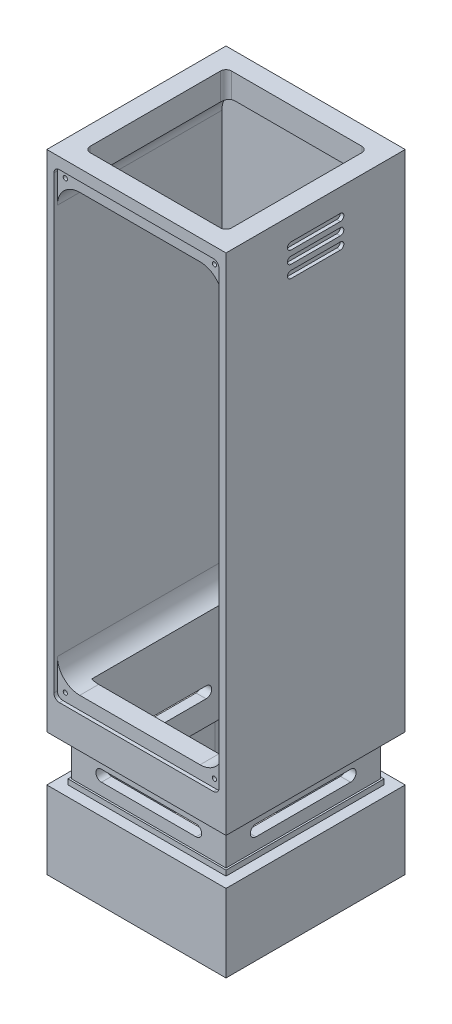
SolidWorks part; units mm, degrees
ref_plane "Front Plane" through (0, 0, 0) normal (0, 0, 1) x (1, 0, 0)
ref_plane "Top Plane" through (0, 0, 0) normal (0, 1, 0) x (1, 0, 0)
ref_plane "Right Plane" through (0, 0, 0) normal (1, 0, 0) x (0, 0, -1)
sketch "Sketch1" plane through (0, 0, 0) normal (0, 1, 0) x (1, 0, 0)
  line L0 (6.35, 44.45) -> (44.45, 44.45)
  line L1 (0, 0) -> (50.8, 0)
  line L2 (0, 0) -> (0, 50.8)
  line L3 (0, 50.8) -> (50.8, 50.8)
  line L4 (50.8, 0) -> (50.8, 50.8)
  line L5 (44.45, 6.35) -> (44.45, 44.45)
  line L6 (6.35, 6.35) -> (44.45, 6.35)
  line L7 (6.35, 6.35) -> (6.35, 44.45)
  dimension "D1" = 50.8
  dimension "D2" = 6.35
extrude "Boss-Extrude1" add sketch "Sketch1" along normal blind 178
sketch "Sketch2" plane through (0, 0, 0) normal (0, -1, 0) x (1, 0, 0)
  line L0 (47.8, -3) -> (3, -3)
  line L1 (3, -3) -> (3, -47.8)
  line L2 (3, -47.8) -> (47.8, -47.8)
  line L3 (47.8, -47.8) -> (47.8, -3)
  line L4 (6.35, -44.45) -> (44.45, -44.45)
  line L5 (6.35, -6.35) -> (6.35, -44.45)
  line L6 (44.45, -6.35) -> (6.35, -6.35)
  line L7 (44.45, -44.45) -> (44.45, -6.35)
  line L8 (6.35, -44.45) -> (44.45, -44.45)
  line L9 (6.35, -6.35) -> (6.35, -44.45)
  line L10 (44.45, -6.35) -> (6.35, -6.35)
  line L11 (44.45, -44.45) -> (44.45, -6.35)
  line L12 (0, -50.8) -> (0, 0) construction
  dimension "D2" = 3
  dimension "D1" = 0
extrude "Cut-Extrude1" cut sketch "Sketch2" against normal blind 20
sketch "Sketch3" plane through (0, 0, 0) normal (0, 0, 1) x (1, 0, 0)
  line L0 (0, 0) -> (50.8, 0) construction
  line L1 (2, 171.15) -> (48.8, 171.15)
  line L2 (2, 171.15) -> (2, 47.675)
  line L3 (2, 47.675) -> (48.8, 47.675)
  line L4 (48.8, 171.15) -> (48.8, 47.675)
  line L5 (0, 178) -> (0, 0) construction
  line L6 (50.8, 178) -> (50.8, 0) construction
  line L7 (0, 178) -> (50.8, 178) construction
  dimension "D1" = 47.675
  dimension "D2" = 2
  dimension "D3" = 2
  dimension "D4" = 6.85
extrude "Cut-Extrude2" cut sketch "Sketch3" against normal blind 47.625
sketch "Sketch4" plane through (0, 0, 0) normal (0, 0, 1) x (1, 0, 0)
  line L0 (0, 178) -> (0, 0) construction
  line L2 (0, 40) -> (0, 24)
  line L3 (0, 24) -> (50.8, 24)
  line L4 (50.8, 40) -> (50.8, 24)
  line L5 (50.8, 178) -> (50.8, 0) construction
  line L6 (0, 0) -> (50.8, 0) construction
  line L10 (0, 40) -> (50.8, 40)
  dimension "D1" = 24
  dimension "D2" = 16
extrude "Cut-Extrude3" [suppressed] cut sketch "Sketch4" against normal blind 3.175
sketch "Sketch5" [suppressed] plane through (0, 0, 0) normal (0, 0, 1) x (1, 0, 0)
  line L0 (50.8, 40) -> (0, 40) construction
  line L3 (0, 40) -> (3, 40)
  line L5 (0, 24) -> (50.8, 24) construction
  line L8 (0, 24) -> (3, 24)
  line L10 (0, 40) -> (0, 24)
  line L11 (3, 40) -> (3, 24)
  line L12 (0, 24) -> (0, 0) construction
  dimension "D1" = 3
extrude "Cut-Extrude4" [suppressed] cut sketch "Sketch5" against normal through all
ref_plane "Plane1" through (0, 0, -25.4) normal (0, 0, 1) x (1, 0, 0)
ref_plane "Plane2" through (25.4, 0, 0) normal (-1, 0, 0) x (0, 0, 1)
sketch "Sketch6" plane through (0, 0, 0) normal (-1, 0, 0) x (0, 0, 1)
  line L0 (-32.4, 170.5) -> (-18.4, 170.5) construction
  line L1 (-32.4, 171.5) -> (-18.4, 171.5)
  line L2 (-32.4, 169.5) -> (-18.4, 169.5)
  line L3 (-32.4, 167) -> (-18.4, 167) construction
  line L4 (-32.4, 168) -> (-18.4, 168)
  line L5 (-32.4, 166) -> (-18.4, 166)
  line L6 (-32.4, 163.5) -> (-18.4, 163.5) construction
  line L9 (-32.4, 164.5) -> (-18.4, 164.5)
  line L10 (-32.4, 162.5) -> (-18.4, 162.5)
  line L11 (-25.4, 170.5) -> (-25.4, 167) construction
  line L12 (-25.4, 167) -> (-25.4, 163.5) construction
  line L13 (-25.4, 170.5) -> (-25.4, 178) construction
  line L14 (-50.8, 178) -> (0, 178) construction
  arc A0 (-32.4, 171.5) -> (-32.4, 169.5) centre (-32.4, 170.5) ccw
  arc A1 (-18.4, 169.5) -> (-18.4, 171.5) centre (-18.4, 170.5) ccw
  arc A2 (-32.4, 168) -> (-32.4, 166) centre (-32.4, 167) ccw
  arc A3 (-18.4, 166) -> (-18.4, 168) centre (-18.4, 167) ccw
  arc A6 (-32.4, 164.5) -> (-32.4, 162.5) centre (-32.4, 163.5) ccw
  arc A7 (-18.4, 162.5) -> (-18.4, 164.5) centre (-18.4, 163.5) ccw
  point P2 (-25.4, 170.5)
  point P9 (-25.4, 167)
  point P16 (-25.4, 163.5)
  point P25 (-33.4, 163.5)
  point P26 (-17.4, 163.5)
  dimension "D1" = 3.5
  dimension "D2" = 2
  dimension "D3" = 7.5
  dimension "D4" = 16
extrude "Cut-Extrude5" cut sketch "Sketch6" against normal blind 1
mirror "Mirror1" [suppressed] about plane through (0, 0, -25.4) normal (0, 0, 1)
mirror "Mirror2" about plane through (25.4, 0, 0) normal (-1, 0, 0) of "Cut-Extrude5", "Cut-Extrude4"
sketch "Sketch7" plane through (0, 0, 0) normal (0, 0, 1) x (1, 0, 0)
  line L0 (0, 178) -> (50.8, 178) construction
  line L1 (2, 171.15) -> (48.8, 171.15)
  line L2 (2, 171.15) -> (2, 174.825)
  line L3 (2, 174.825) -> (48.8, 174.825)
  line L4 (48.8, 171.15) -> (48.8, 174.825)
  line L6 (2, 47.675) -> (48.8, 47.675)
  line L7 (2, 47.675) -> (2, 44)
  line L8 (2, 44) -> (48.8, 44)
  line L9 (48.8, 47.675) -> (48.8, 44)
  dimension "D1" = 3.175
extrude "Cut-Extrude6" cut sketch "Sketch7" against normal blind 1
fillet "Fillet1" radius 1.5875 4 edges at (48.8, 174.825, -0.5) (2, 174.825, -0.5) (48.8, 44, -0.5) (2, 44, -0.5)
sketch "Sketch8" plane through (0, 178, 0) normal (0, 1, 0) x (1, 0, 0)
  line L1 (6.9375, 45.45) -> (43.8625, 45.45)
  line L2 (5.35, 43.8625) -> (5.35, 6.9375)
  line L3 (6.9375, 5.35) -> (43.8625, 5.35)
  line L4 (45.45, 43.8625) -> (45.45, 6.9375)
  line L8 (6.35, 44.45) -> (6.35, 6.35) construction
  line L10 (6.35, 6.35) -> (44.45, 6.35) construction
  line L11 (44.45, 6.35) -> (44.45, 44.45) construction
  arc A0 (43.8625, 45.45) -> (45.45, 43.8625) centre (43.8625, 43.8625) cw
  arc A1 (45.45, 6.9375) -> (43.8625, 5.35) centre (43.8625, 6.9375) cw
  arc A2 (6.9375, 5.35) -> (5.35, 6.9375) centre (6.9375, 6.9375) cw
  arc A3 (5.35, 43.8625) -> (6.9375, 45.45) centre (6.9375, 43.8625) cw
  dimension "D1" = 1.5875
  dimension "D2" = 1
  dimension "D3" = 1
  dimension "D4" = 1
extrude "Cut-Extrude7" cut sketch "Sketch8" against normal up to next
hole_wizard "#0-80 Tapped Hole1" positions "Sketch12" profile "Sketch14" tap size "#0-80" standard "ANSI Inch"
sketch "Sketch12" plane through (0, 0, -1) normal (0, 0, 1) x (1, 0, 0)
  line L2 (4.2542, 172.571) -> (4.2542, 46.286) construction
  line L3 (4.2542, 46.286) -> (46.5138, 46.286) construction
  line L4 (46.5138, 46.286) -> (46.5138, 172.571) construction
  line L5 (46.5138, 172.571) -> (4.2542, 172.571) construction
  line L8 (0, 178) -> (0, 0) construction
  line L9 (0, 178) -> (50.8, 178) construction
  line L10 (50.8, 178) -> (50.8, 0) construction
  point P0 (4.2542, 172.571)
  point P3 (46.5138, 172.571)
  point P6 (4.2542, 46.286)
  point P9 (46.5138, 46.286)
  dimension "D1" = 4.2542
  dimension "D2" = 5.429
  dimension "D3" = 4.2862
  dimension "D4" = 126.285
sketch "Sketch14" plane through (4.2542, 172.571, -1) normal (1, 0, 0) x (0, -1, 0)
  line L0 (0, 0) -> (0, 3.3576)
  line L1 (0, 3.3576) -> (0.5956, 2.9997)
  line L2 (0.5956, 2.9997) -> (0.5956, 0)
  line L5 (0.5956, 0) -> (0, 0)
  line L10 (0, 3.3576) -> (-0.5956, 2.9997) construction
  line L11 (0, -6.35) -> (0, 107.95) construction
  dimension "Tap Drill Dia." = 1.1913
  dimension "Tap Drill Depth" = 2.9997
  dimension "Drill Angle" = 118
cosmetic thread "Hole Thread5" parameters "D1"=3.048, "D2"=1.524
cosmetic thread "Hole Thread6" parameters "D1"=3.048, "D2"=1.524
cosmetic thread "Hole Thread7" parameters "D1"=3.048, "D2"=1.524
cosmetic thread "Hole Thread8" parameters "D1"=3.048, "D2"=1.524
sketch "Sketch15" [suppressed] plane through (0, 0, -3.175) normal (0, 0, 1) x (1, 0, 0)
  line L0 (11.9875, 32) -> (38.8125, 32) construction
  line L1 (11.9875, 33.5875) -> (38.8125, 33.5875)
  line L2 (11.9875, 30.4125) -> (38.8125, 30.4125)
  line L3 (11.9875, 32) -> (3, 32) construction
  line L4 (3, 24) -> (3, 40) construction
  line L5 (38.8125, 32) -> (47.8, 32) construction
  line L6 (47.8, 24) -> (47.8, 40) construction
  arc A0 (11.9875, 33.5875) -> (11.9875, 30.4125) centre (11.9875, 32) ccw
  arc A1 (38.8125, 30.4125) -> (38.8125, 33.5875) centre (38.8125, 32) ccw
  point P2 (25.4, 32)
  point P17 (10.4, 32)
  point P18 (40.4, 32)
  dimension "D1" = 3.175
  dimension "D2" = 30
extrude "Cut-Extrude8" [suppressed] cut sketch "Sketch15" against normal through all
sketch "Sketch16" [suppressed] plane through (3, 0, 0) normal (-1, 0, 0) x (0, 0, 1)
  line L0 (-38.8125, 32) -> (-11.9875, 32) construction
  line L1 (-38.8125, 33.5875) -> (-11.9875, 33.5875)
  line L2 (-38.8125, 30.4125) -> (-11.9875, 30.4125)
  line L3 (-38.8125, 32) -> (-47.625, 32) construction
  line L4 (-47.625, 24) -> (-47.625, 40) construction
  line L5 (-11.9875, 32) -> (-3.175, 32) construction
  line L6 (-3.175, 24) -> (-3.175, 40) construction
  arc A0 (-38.8125, 33.5875) -> (-38.8125, 30.4125) centre (-38.8125, 32) ccw
  arc A1 (-11.9875, 30.4125) -> (-11.9875, 33.5875) centre (-11.9875, 32) ccw
  point P2 (-25.4, 32)
  point P15 (-40.4, 32)
  point P16 (-10.4, 32)
  dimension "D1" = 3.175
  dimension "D2" = 30
extrude "Cut-Extrude9" [suppressed] cut sketch "Sketch16" against normal through all
sketch "Sketch17" [suppressed] plane through (0, 0, -3.175) normal (0, 0, 1) x (1, 0, 0)
  line L0 (3, 24) -> (3, 40) construction
  line L1 (3, 37.0668) -> (47.8, 37.0668)
  line L2 (3, 37.0668) -> (3, 27.0668)
  line L3 (3, 27.0668) -> (47.8, 27.0668)
  line L4 (47.8, 37.0668) -> (47.8, 27.0668)
  line L5 (47.8, 24) -> (47.8, 40) construction
  dimension "D1" = 10
extrude "Cut-Extrude10" [suppressed] cut sketch "Sketch17" against normal blind 0.5
sketch "Sketch18" [suppressed] plane through (0, 0, -3.175) normal (0, 0, 1) x (1, 0, 0)
  line L0 (8.6937, 29) -> (42.1062, 29) construction
  line L1 (8.6937, 29.7938) -> (42.1062, 29.7938)
  line L2 (8.6937, 28.2062) -> (42.1062, 28.2062)
  line L3 (25.4, 29) -> (25.4, 24) construction
  line L4 (0, 24) -> (50.8, 24) construction
  line L5 (8.6937, 35) -> (42.1062, 35) construction
  line L6 (8.6937, 35.7938) -> (42.1062, 35.7938)
  line L7 (8.6937, 34.2063) -> (42.1062, 34.2063)
  line L8 (25.4, 35) -> (25.4, 29) construction
  line L9 (3, 24) -> (47.8, 24) construction
  line L10 (47.8, 40) -> (3, 40) construction
  arc A0 (8.6937, 29.7938) -> (8.6937, 28.2062) centre (8.6937, 29) ccw
  arc A1 (42.1062, 28.2062) -> (42.1062, 29.7938) centre (42.1062, 29) ccw
  arc A2 (8.6937, 35.7938) -> (8.6937, 34.2063) centre (8.6937, 35) ccw
  arc A3 (42.1062, 34.2063) -> (42.1062, 35.7938) centre (42.1062, 35) ccw
  point P2 (25.4, 29)
  point P8 (7.9, 29)
  point P9 (42.9, 29)
  point P16 (25.4, 35)
  dimension "D1" = 1.5875
  dimension "D2" = 35
  dimension "D3" = 5
  dimension "D4" = 5
extrude "Cut-Extrude11" [suppressed] cut sketch "Sketch18" against normal through all
sketch "Sketch19" plane through (0, 0, 0) normal (0, 0, 1) x (1, 0, 0)
  line L0 (0, 178) -> (0, 0) construction
  line L1 (0, 22) -> (50.8, 22)
  line L2 (0, 22) -> (0, 35)
  line L3 (0, 35) -> (50.8, 35)
  line L4 (50.8, 22) -> (50.8, 35)
  line L5 (50.8, 178) -> (50.8, 0) construction
  line L6 (0, 0) -> (50.8, 0) construction
  dimension "D1" = 22
  dimension "D2" = 13
extrude "Cut-Extrude12" cut sketch "Sketch19" against normal blind 3
ref_axis "Axis1" through (25.4, 29.5429, -25.4) along (0, -1, 0)
sketch "Sketch20" plane through (0, 0, -3) normal (0, 0, 1) x (1, 0, 0)
  line L0 (11.9875, 28.5) -> (38.8125, 28.5) construction
  line L1 (11.9875, 30.0875) -> (38.8125, 30.0875)
  line L2 (11.9875, 26.9125) -> (38.8125, 26.9125)
  line L3 (38.8125, 28.5) -> (0, 28.5) construction
  line L4 (25.4, 28.5) -> (25.4, 22) construction
  line L5 (0, 22) -> (50.8, 22) construction
  line L6 (0, 35) -> (0, 22) construction
  arc A0 (11.9875, 30.0875) -> (11.9875, 26.9125) centre (11.9875, 28.5) ccw
  arc A1 (38.8125, 26.9125) -> (38.8125, 30.0875) centre (38.8125, 28.5) ccw
  point P2 (25.4, 28.5)
  point P9 (10.4, 28.5)
  point P10 (40.4, 28.5)
  dimension "D1" = 30
  dimension "D2" = 3.175
extrude "Cut-Extrude13" cut sketch "Sketch20" against normal up to next
sketch "Sketch21" plane through (0, 0, -3) normal (0, 0, 1) x (1, 0, 0)
  line L0 (0, 35) -> (0, 22) construction
  line L1 (0, 33.5) -> (50.8, 33.5)
  line L2 (0, 33.5) -> (0, 23.5)
  line L3 (0, 23.5) -> (50.8, 23.5)
  line L4 (50.8, 33.5) -> (50.8, 23.5)
  line L5 (50.8, 22) -> (50.8, 35) construction
  point P9 (50.8, 28.5)
  dimension "D1" = 10
extrude "Cut-Extrude14" cut sketch "Sketch21" against normal blind 0.5
pattern_circular "CirPattern1" count 4 over 360 about axis through (25.4, 29.5429, -25.4) along (0, -1, 0) of "Cut-Extrude12", "Cut-Extrude13", "Cut-Extrude14"
sketch "Sketch22" [suppressed] plane through (0, 0, 0) normal (-1, 0, 0) x (0, 0, 1)
  line L0 (-40.4, 140.6) -> (-10.4, 140.6)
  line L1 (-40.4, 140.6) -> (-40.4, 101)
  line L2 (-40.4, 101) -> (-10.4, 101)
  line L3 (-10.4, 140.6) -> (-10.4, 101)
  line L8 (-25.4, 101) -> (-25.4, 35) construction
  line L9 (-50.8, 35) -> (0, 35) construction
  line L10 (-50.8, 0) -> (0, 0) construction
  point P10 (-25.4, 101)
  dimension "D1" = 39.6
  dimension "D2" = 30
  dimension "D4" = 101
extrude "Cut-Extrude15" [suppressed] cut sketch "Sketch22" against normal up to next
fillet "Fillet2" radius 3.175 4 edges at (3, 10, -47.8) (3, 10, -3) (47.8, 10, -3) (47.8, 10, -47.8)
fillet "Fillet3" radius 6.35 4 edges at (2, 171.15, -24.3125) (48.8, 171.15, -24.3125) (2, 47.675, -24.3125) (48.8, 47.675, -24.3125)
sketch "Sketch23" [suppressed] plane through (0, 0, -50.8) normal (0, 0, -1) x (-1, 0, 0)
  line L0 (-25.4, 138) -> (-25.4, 178) construction
  line L1 (-40.4, 138) -> (-10.4, 138)
  line L2 (-40.4, 138) -> (-40.4, 58.8)
  line L3 (-40.4, 58.8) -> (-10.4, 58.8)
  line L4 (-10.4, 138) -> (-10.4, 58.8)
  line L5 (-50.8, 178) -> (0, 178) construction
  line L6 (-50.8, 0) -> (0, 0) construction
  dimension "D1" = 30
  dimension "D2" = 79.2
  dimension "D3" = 58.8
extrude "Cut-Extrude16" [suppressed] cut sketch "Sketch23" against normal up to next
sketch "Sketch24" [suppressed] plane through (0, 0, -50.8) normal (0, 0, -1) x (-1, 0, 0)
  line L0 (-25.4, 49) -> (-25.4, 35) construction
  line L1 (-28.29, 52.16) -> (-22.51, 52.16)
  line L2 (-28.29, 49) -> (-22.51, 49)
  line L3 (-50.8, 35) -> (0, 35) construction
  line L4 (-50.8, 0) -> (0, 0) construction
  arc A0 (-28.29, 52.16) -> (-28.29, 49) centre (-28.29, 50.58) ccw
  arc A1 (-22.51, 52.16) -> (-22.51, 49) centre (-22.51, 50.58) cw
  point P9 (-29.87, 50.58)
  point P10 (-20.93, 50.58)
  dimension "D1" = 3.16
  dimension "D2" = 8.94
  dimension "D3" = 49
extrude "Cut-Extrude17" [suppressed] cut sketch "Sketch24" against normal up to next
